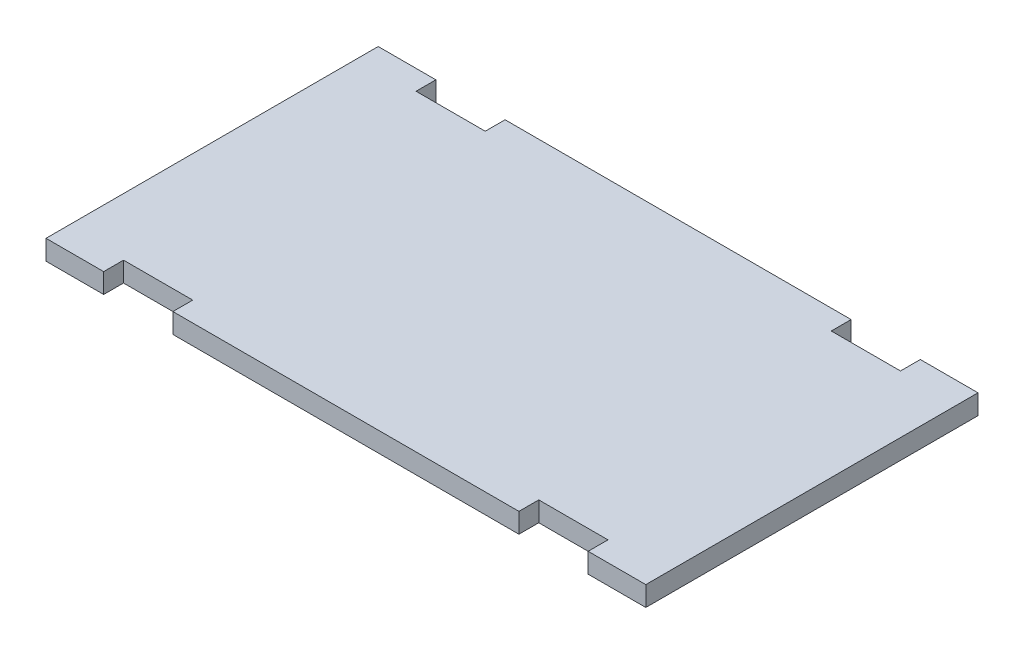
SolidWorks part; units mm, degrees
ref_plane "Front Plane" through (0, 0, 0) normal (0, 0, 1) x (1, 0, 0)
ref_plane "Top Plane" through (0, 0, 0) normal (0, 1, 0) x (1, 0, 0)
ref_plane "Right Plane" through (0, 0, 0) normal (1, 0, 0) x (0, 0, -1)
sketch "Sketch1" plane through (0, 0, 0) normal (0, 1, 0) x (1, 0, 0)
  line L1 (-47.5, 40) -> (47.5, 40)
  line L2 (-55, 32.5) -> (-55, -32.5)
  line L3 (-47.5, -40) -> (47.5, -40)
  line L4 (55, 32.5) -> (55, -32.5)
  line L5 (-55, 40) -> (55, -40) construction
  line L6 (-55, -40) -> (55, 40) construction
  line L7 (-82.55, 45.461) -> (82.55, 45.461)
  line L8 (-82.55, 45.461) -> (-82.55, -45.979)
  line L9 (-82.55, -45.979) -> (82.55, -45.979)
  line L10 (82.55, 45.461) -> (82.55, -45.979)
  line L11 (-82.55, 45.461) -> (82.55, -45.979) construction
  line L12 (-82.55, -45.979) -> (82.55, 45.461) construction
  arc A0 (47.5, -40) -> (55, -32.5) centre (47.5, -32.5) ccw
  arc A1 (55, 32.5) -> (47.5, 40) centre (47.5, 32.5) ccw
  arc A2 (-47.5, 40) -> (-55, 32.5) centre (-47.5, 32.5) ccw
  arc A3 (-47.5, -40) -> (-55, -32.5) centre (-47.5, -32.5) cw
  point P0 (0, 0)
  point P18 (0, 0)
  point P25 (0, -0.259)
  dimension "D3" = 7.5
  dimension "D1" = 80
  dimension "D2" = 110
  dimension "D4" = 5.461
  dimension "D5" = 165.1
  dimension "D6" = 5.979
  dimension "D7" = 91.44
extrude "Boss-Extrude1" add sketch "Sketch1" along normal blind 5.461
sketch "Sketch2" plane through (0, 5.461, 0) normal (0, 1, 0) x (1, 0, 0)
  line L0 (82.55, 45.461) -> (-82.55, 45.461) construction
  line L1 (-66.675, 45.461) -> (-47.625, 45.461)
  line L2 (-66.675, 45.461) -> (-66.675, 40)
  line L3 (-66.675, 40) -> (-47.625, 40)
  line L4 (-47.625, 45.461) -> (-47.625, 40)
  line L5 (-82.55, -45.979) -> (82.55, -45.979) construction
  line L6 (-66.675, -45.979) -> (-47.625, -45.979)
  line L7 (-66.675, -45.979) -> (-66.675, -40.518)
  line L8 (-66.675, -40.518) -> (-47.625, -40.518)
  line L9 (-47.625, -45.979) -> (-47.625, -40.518)
  line L10 (47.625, -45.979) -> (66.675, -45.979)
  line L11 (47.625, -45.979) -> (47.625, -40.518)
  line L12 (47.625, -40.518) -> (66.675, -40.518)
  line L13 (66.675, -45.979) -> (66.675, -40.518)
  line L14 (-82.55, 45.461) -> (-82.55, -45.979) construction
  line L15 (47.625, 45.461) -> (66.675, 45.461)
  line L16 (47.625, 45.461) -> (47.625, 40)
  line L17 (47.625, 40) -> (66.675, 40)
  line L18 (66.675, 45.461) -> (66.675, 40)
  line L19 (82.55, -45.979) -> (82.55, 45.461) construction
  dimension "D1" = 5.461
  dimension "D2" = 19.05
  dimension "D3" = 15.875
  dimension "D4" = 15.875
extrude "Cut-Extrude1" cut sketch "Sketch2" against normal through all
extrude "Boss-Extrude2" add sketch "Sketch1<3>" along normal up to surface (5.461 mm away) contours L2 A3 L3 A0 L4 A1 L1 A2 up to face at (0, 5.461, 0.259)
sketch "Sketch1<3>" plane through (0, 0, 0) normal (0, 1, 0) x (1, 0, 0) same geometry as "Sketch1"
equation "\"D4@Sketch2\"=\"D3@Sketch2\""
